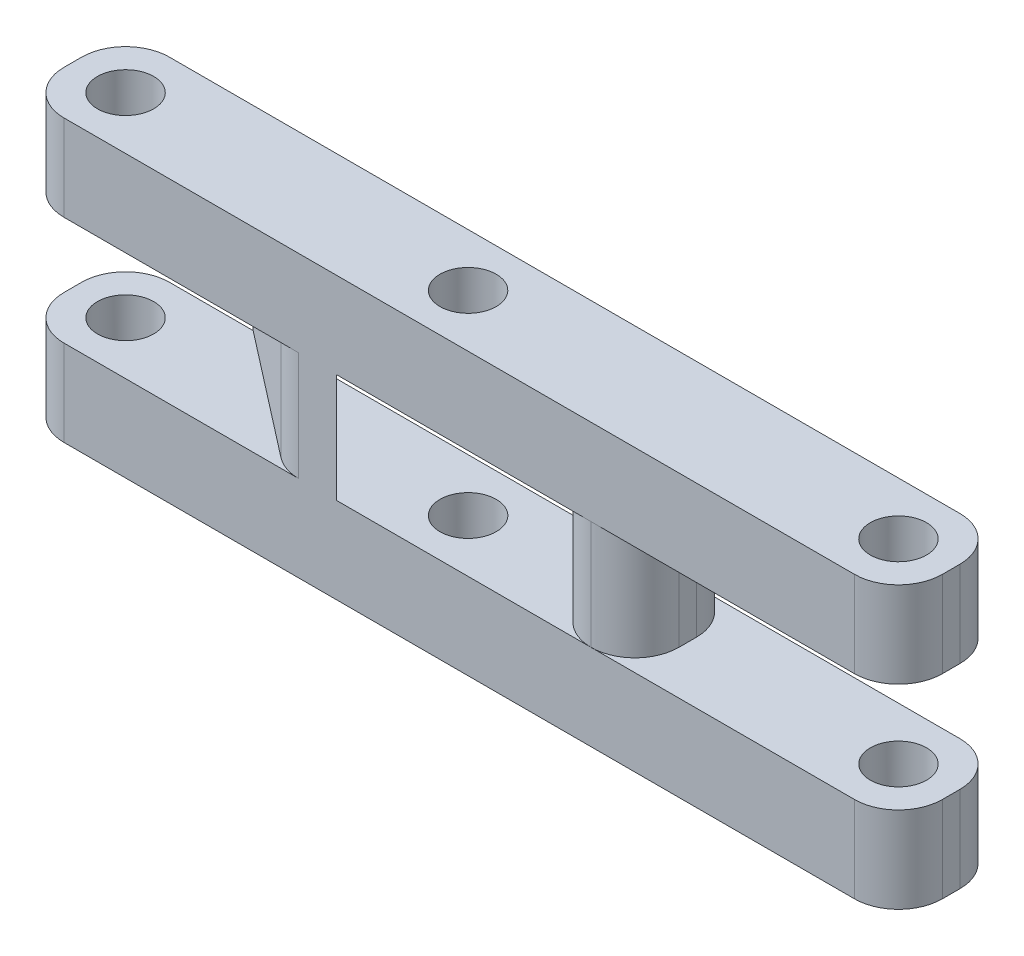
SolidWorks part; units mm, degrees
ref_plane "Front Plane" through (0, 0, 0) normal (0, 0, 1) x (1, 0, 0)
ref_plane "Top Plane" through (0, 0, 0) normal (0, 1, 0) x (1, 0, 0)
ref_plane "Right Plane" through (0, 0, 0) normal (1, 0, 0) x (0, 0, -1)
sketch "Sketch1" plane through (0, 0, 0) normal (0, 1, 0) x (1, 0, 0)
  line L1 (-25, -3) -> (25, -3)
  line L2 (-25, -3) -> (-25, 3)
  line L3 (-25, 3) -> (25, 3)
  line L4 (25, -3) -> (25, 3)
  line L5 (-25, -3) -> (25, 3) construction
  line L6 (-25, 3) -> (25, -3) construction
  point P0 (0, 0)
  dimension "D1" = 6
  dimension "D2" = 50
extrude "Boss-Extrude1" add sketch "Sketch1" along normal mid plane 16
sketch "Sketch2" plane through (0, 0, 0) normal (0, 1, 0) x (1, 0, 0)
  line L0 (-25, -3) -> (25, -3) construction
  line L1 (-25, -3) -> (-10, -3)
  line L2 (-25, -3) -> (-25, 3)
  line L3 (-25, 3) -> (-17.7361, 3)
  line L4 (-10, -3) -> (-17.7361, 3)
  line L5 (25, 3) -> (10, 3)
  line L6 (25, 3) -> (25, -3)
  line L7 (25, -3) -> (10, -3)
  line L8 (10, 3) -> (10, -3)
  line L9 (25, 3) -> (-25, 3) construction
  line L11 (5, 3) -> (-14.7361, 3)
  line L12 (5, 3) -> (5, -3)
  line L13 (5, -3) -> (-7, -3)
  line L14 (-14.7361, 3) -> (-7, -3)
  point P18 (-17.1002, 3)
  point P19 (0, 0)
  point P20 (-14.0993, 3)
  point P21 (-13.923, 3)
  point P22 (0, 0)
  point P23 (-12.7361, 3)
  dimension "D1" = 15
  dimension "D2" = 20
  dimension "D3" = 12
  dimension "D4" = 15
extrude "Cut-Extrude1" cut sketch "Sketch2" against normal mid plane 6.2
sketch "Sketch3" plane through (0, 0, 0) normal (0, 1, 0) x (1, 0, 0)
  line L0 (-25, 3) -> (-25, -3) construction
  line L1 (25, -3) -> (25, 3) construction
  line L2 (-25, 0) -> (-22, 0) construction
  line L3 (22, 0) -> (25, 0) construction
  line L4 (5, -3) -> (5, 3) construction
  circle A0 centre (-22, 0) radius 1.6
  circle A1 centre (22, 0) radius 1.6
  circle A2 centre (-2.5, 0) radius 1.6
  point P7 (-25, 0)
  point P11 (25, 0)
  point P20 (-2.5, 0)
  dimension "D1" = 3.2
  dimension "D2" = 3
  dimension "D3" = 7.5
extrude "Cut-Extrude2" cut sketch "Sketch3" against normal through all both and the other way through all
fillet "Fillet1" radius 2.5 14 edges at (-14.7361, 0, -3) (-10, 0, 3) (5, 0, 3) (5, 0, -3) (10, 0, 3) (10, 0, -3) (25, 5.55, 3) (25, 5.55, -3) (-25, 5.55, 3) (-25, 5.55, -3) (25, -5.55, -3) (-25, -5.55, 3) (25, -5.55, 3) (-25, -5.55, -3)
